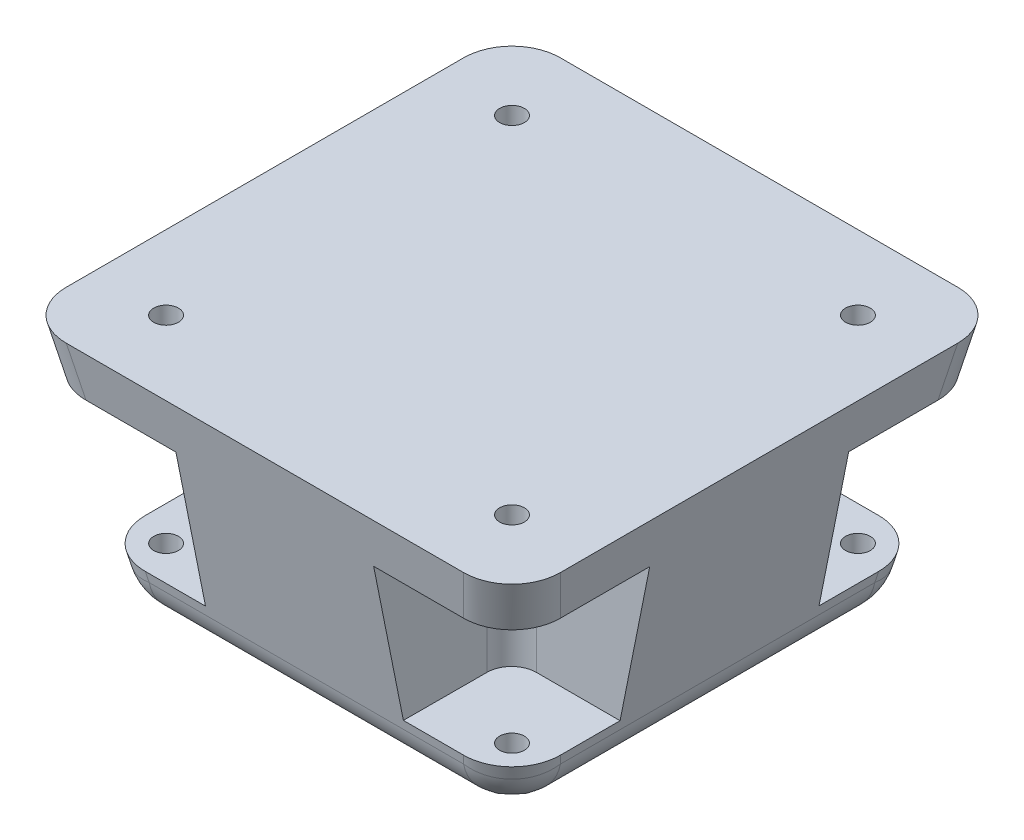
SolidWorks part; units mm, degrees
ref_plane "Front Plane" through (0, 0, 0) normal (0, 0, 1) x (1, 0, 0)
ref_plane "Top Plane" through (0, 0, 0) normal (0, 1, 0) x (1, 0, 0)
ref_plane "Right Plane" through (0, 0, 0) normal (1, 0, 0) x (0, 0, -1)
sketch "Sketch2" plane through (0, 0, 0) normal (0, 1, 0) x (1, 0, 0)
  line L1 (-500, 500) -> (500, 500)
  line L2 (-500, 500) -> (-500, -500)
  line L3 (-500, -500) -> (500, -500)
  line L4 (500, 500) -> (500, -500)
  line L5 (-500, 500) -> (500, -500) construction
  line L6 (-500, -500) -> (500, 500) construction
  point P0 (0, 0)
  dimension "D1" = 1000
  dimension "D2" = 1000
extrude "Boss-Extrude1" add sketch "Sketch2" along normal blind 500
ref_plane "Plane1" through (0, 0, 510) normal (0, 0, 1) x (1, 0, 0)
sketch "Sketch4" plane through (0, 0, 500) normal (0, 0, 1) x (1, 0, 0)
  line L0 (-500, 500) -> (500, 500) construction
  line L1 (500, 500) -> (500, 0) construction
  line L2 (-500, 500) -> (500, 500) construction
  line L3 (-400, 0) -> (400, 0)
  line L4 (-500, 0) -> (500, 0) construction
  line L5 (400, 0) -> (500, 500)
  line L6 (-400, 0) -> (-500, 500)
  line L7 (500, 500) -> (-500, 500)
  point P13 (0, 0)
  dimension "D1" = 800
extrude "Cut-Extrude1" cut sketch "Sketch4" against normal through all both and the other way through all flip side to cut
ref_plane "Plane2" through (0, 0, 0) normal (1, 0, 0) x (0, 0, -1)
sketch "Sketch6" plane through (0, 0, 0) normal (1, 0, 0) x (0, 0, -1)
  line L0 (-400, 0) -> (400, 0)
  line L1 (500, 0) -> (-500, 0) construction
  line L2 (-400, 0) -> (-500, 500)
  line L3 (-500, 500) -> (500, 500)
  line L4 (500, 500) -> (400, 0)
  point P6 (0, 0)
  dimension "D1" = 800
extrude "Cut-Extrude2" cut sketch "Sketch6" against normal through all both and the other way through all flip side to cut contours L4 L0 L2 L3
fillet "Fillet1" radius 100 8 edges at (0, 0, 400) (0, 0, -400) (-450, 250, 450) (-450, 250, -450) (-400, 0, 0) (400, 0, 0) (450, 250, 450) (450, 250, -450)
ref_plane "Plane4" through (0, 250, 0) normal (0, 1, 0) x (1, 0, 0)
sketch "Sketch8" plane through (0, 250, 0) normal (0, 1, 0) x (1, 0, 0)
  line L0 (-500, -201.3008) -> (-200.7785, -201.3008) construction
  line L1 (-500, -501.3008) -> (500, -501.3008) construction
  line L2 (-500, -501.3008) -> (-500, 501.3008) construction
  line L3 (-500, 501.3008) -> (500, 501.3008) construction
  line L4 (500, -501.3008) -> (500, 501.3008) construction
  line L5 (-500, -501.3008) -> (500, 501.3008) construction
  line L6 (-500, 501.3008) -> (500, -501.3008) construction
  line L7 (-200.7785, -201.3008) -> (-200, -501.3008) construction
  line L8 (-500, -201.3008) -> (-250.6489, -201.3008)
  line L9 (-200.6491, -251.1711) -> (-200, -501.3008)
  line L10 (-500, -201.3008) -> (-500, -501.3008)
  line L11 (-500, -501.3008) -> (-200, -501.3008)
  line L12 (-500, 0) -> (500, 0) construction
  line L13 (0, 501.3008) -> (0, -501.3008) construction
  line L14 (500, -201.3008) -> (500, -501.3008)
  line L15 (500, -201.3008) -> (250.6489, -201.3008)
  line L16 (200.6491, -251.1711) -> (200, -501.3008)
  line L17 (500, -501.3008) -> (200, -501.3008)
  line L18 (500, 201.3008) -> (250.6489, 201.3008)
  line L19 (200.6491, 251.1711) -> (200, 501.3008)
  line L20 (500, 501.3008) -> (200, 501.3008)
  line L21 (500, 201.3008) -> (500, 501.3008)
  line L22 (-500, 201.3008) -> (-500, 501.3008)
  line L23 (-500, 201.3008) -> (-250.6489, 201.3008)
  line L24 (-200.6491, 251.1711) -> (-200, 501.3008)
  line L25 (-500, 501.3008) -> (-200, 501.3008)
  line L26 (-500, 501.3008) -> (-200.6491, 201.1711) construction
  arc A0 (-200.6491, -251.1711) -> (-250.6489, -201.3008) centre (-250.6489, -251.3008) ccw
  arc A1 (200.6491, -251.1711) -> (250.6489, -201.3008) centre (250.6489, -251.3008) cw
  arc A2 (200.6491, 251.1711) -> (250.6489, 201.3008) centre (250.6489, 251.3008) ccw
  arc A3 (-200.6491, 251.1711) -> (-250.6489, 201.3008) centre (-250.6489, 251.3008) cw
  point P0 (0, 0)
  point P2 (-200, -501.3008)
  point P7 (-500, -201.3008)
  point P8 (-300, 501.3008)
  point P11 (330.7003, 501.3008)
  point P13 (500, -301.3008)
  dimension "D3" = 50
  dimension "D1" = 300
  dimension "D2" = 300
extrude "Cut-Extrude4" cut sketch "Sketch8" against normal mid plane 300
sketch "Sketch11" plane through (0, 0, 0) normal (0, -1, 0) x (1, 0, 0)
  line L0 (-500, 500) -> (-200, 500) construction
  line L1 (-500, 500) -> (500, 500)
  line L2 (-500, 500) -> (-500, -500)
  line L3 (-500, -500) -> (500, -500)
  line L4 (500, 500) -> (500, -500)
  line L5 (-500, 500) -> (500, -500) construction
  line L6 (-500, -500) -> (500, 500) construction
  line L7 (-500, 500) -> (-500, 200.3354) construction
  line L8 (-200, 200) -> (-500, 200.3354) construction
  line L9 (-200, 200) -> (-200, 500) construction
  line L10 (-500, 500) -> (-200, 200) construction
  line L11 (-500, 500) -> (-200, 200) construction
  line L12 (-500, 500) -> (-200, 200) construction
  line L13 (-500, 0) -> (500, 0) construction
  line L14 (0, -500) -> (0, 500) construction
  circle A0 centre (-350, 350) radius 25
  circle A1 centre (350, 350) radius 25
  circle A2 centre (350, -350) radius 25
  circle A3 centre (-350, -350) radius 25
  point P0 (0, 0)
  dimension "D4" = 50
  dimension "D1" = 1000
  dimension "D2" = 300
  dimension "D3" = 299.6646
extrude "Cut-Extrude5" cut sketch "Sketch11" against normal through all flip side to cut
